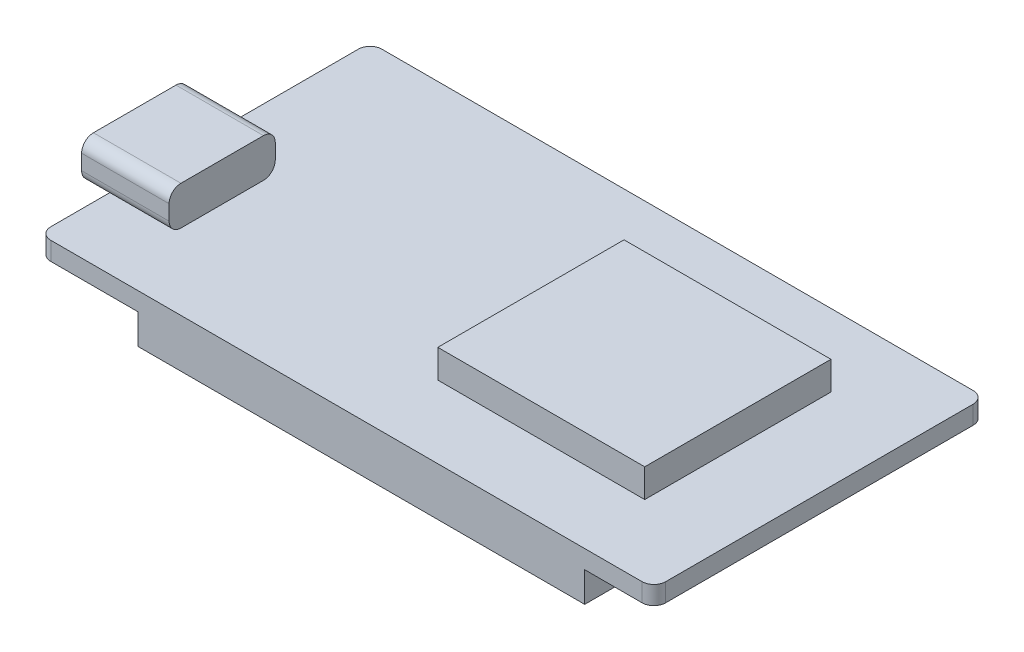
SolidWorks part; units mm, degrees
ref_plane "前基準面" through (0, 0, 0) normal (0, 0, 1) x (1, 0, 0)
ref_plane "上基準面" through (0, 0, 0) normal (0, 1, 0) x (1, 0, 0)
ref_plane "右基準面" through (0, 0, 0) normal (1, 0, 0) x (0, 0, -1)
sketch "草圖1" plane through (0, 0, 0) normal (0, 1, 0) x (1, 0, 0)
  line L1 (-26, 14) -> (26, 14)
  line L2 (-26, 14) -> (-26, -14)
  line L3 (-26, -14) -> (26, -14)
  line L4 (26, 14) -> (26, -14)
  line L5 (-26, 14) -> (26, -14) construction
  line L6 (-26, -14) -> (26, 14) construction
  point P0 (0, 0)
  dimension "D1" = 28
  dimension "D2" = 52
extrude "填料-伸長1" add sketch "草圖1" along normal blind 1.55
fillet "圓角1" radius 1 4 edges at (26, 0.775, -14) (-26, 0.775, -14) (-26, 0.775, 14) (26, 0.775, 14)
sketch "草圖2" plane through (0, 0, 0) normal (0, -1, 0) x (1, 0, 0)
  line L0 (-25, 14) -> (25, 14) construction
  line L1 (-17.61, 14) -> (20.15, 14)
  line L2 (-17.61, 14) -> (-17.61, 11.46)
  line L3 (-17.61, 11.46) -> (20.15, 11.46)
  line L4 (20.15, 14) -> (20.15, 11.46)
  line L5 (26, 13) -> (26, -13) construction
  line L6 (-26, 0) -> (26, 0) construction
  line L7 (-26, -13) -> (-26, 13) construction
  line L8 (20.15, -14) -> (20.15, -11.46)
  line L9 (-17.61, -14) -> (-17.61, -11.46)
  line L10 (-17.61, -14) -> (20.15, -14)
  line L11 (-17.61, -11.46) -> (20.15, -11.46)
  dimension "D1" = 2.54
  dimension "D2" = 37.76
  dimension "D3" = 5.85
extrude "填料-伸長2" add sketch "草圖2" along normal blind 2.54
sketch "草圖3" plane through (0, 1.55, 0) normal (0, 1, 0) x (1, 0, 0)
  line L0 (26, -13) -> (26, 13) construction
  line L1 (1.6, 7.875) -> (19.1, 7.875)
  line L2 (1.6, 7.875) -> (1.6, -7.875)
  line L3 (1.6, -7.875) -> (19.1, -7.875)
  line L4 (19.1, 7.875) -> (19.1, -7.875)
  line L5 (1.6, 7.875) -> (19.1, -7.875) construction
  line L6 (1.6, -7.875) -> (19.1, 7.875) construction
  point P0 (10.35, 0)
  point P5 (4.5014, 0)
  point P7 (11.5976, 0)
  dimension "D1" = 17.5
  dimension "D2" = 15.75
  dimension "D3" = 6.9
extrude "填料-伸長4" add sketch "草圖3" along normal blind 2.4
sketch "草圖5" plane through (-26, 0, 0) normal (-1, 0, 0) x (0, 0, 1)
  line L0 (-13, 1.55) -> (13, 1.55) construction
  line L1 (7.6, 1.55) -> (0.62, 1.55)
  line L2 (8.6, 2.55) -> (8.6, 3.83)
  line L3 (7.6, 4.83) -> (0.62, 4.83)
  line L4 (-0.38, 2.55) -> (-0.38, 3.83)
  line L5 (-7.875, 1.55) -> (7.875, 1.55) construction
  line L6 (14, 1.55) -> (14, 0) construction
  arc A0 (0.62, 4.83) -> (-0.38, 3.83) centre (0.62, 3.83) ccw
  arc A1 (0.62, 1.55) -> (-0.38, 2.55) centre (0.62, 2.55) cw
  arc A2 (7.6, 1.55) -> (8.6, 2.55) centre (7.6, 2.55) ccw
  arc A3 (8.6, 3.83) -> (7.6, 4.83) centre (7.6, 3.83) ccw
  point P6 (-1.0266, 1.55)
  point P13 (-0.38, 4.83)
  point P16 (-0.38, 1.55)
  point P19 (8.6, 1.55)
  point P22 (8.6, 4.83)
  dimension "D4" = 1
  dimension "D1" = 3.28
  dimension "D2" = 8.98
  dimension "D3" = 5.4
extrude "填料-伸長6" add sketch "草圖5" against normal blind 5.6 and the other way blind 1.8
